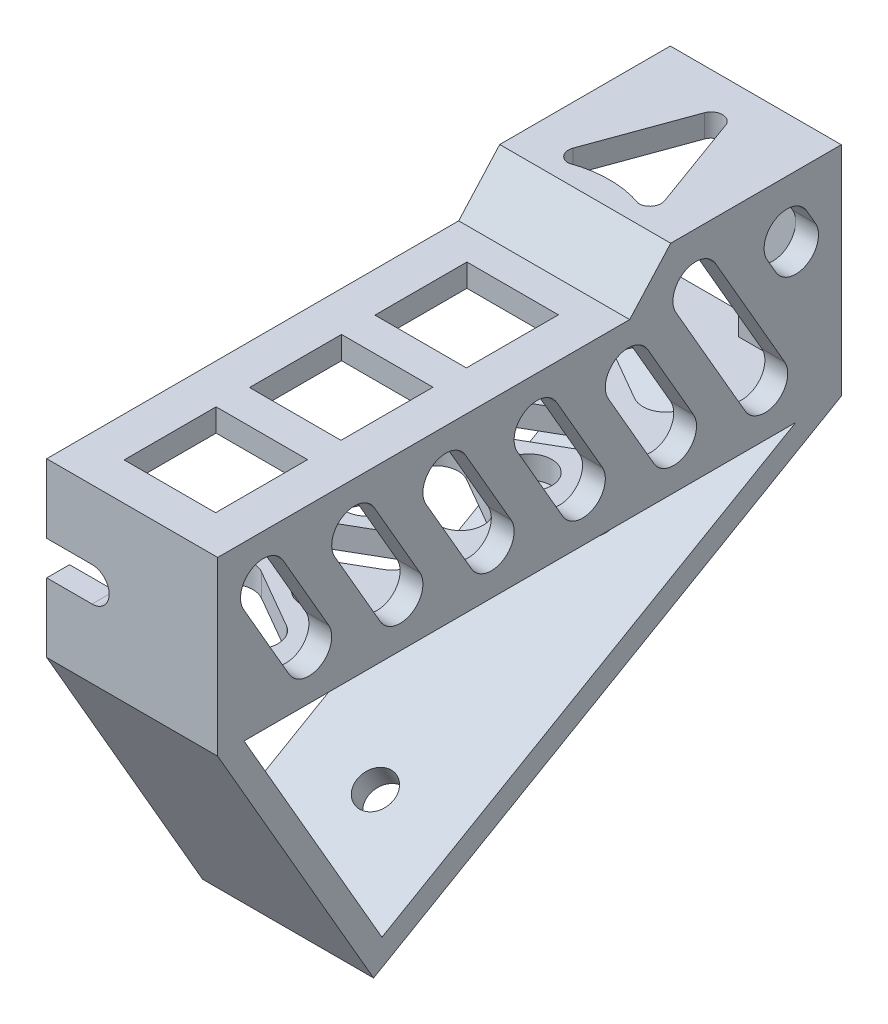
SolidWorks part; units mm, degrees
ref_plane "前视基准面" through (0, 0, 0) normal (0, 0, 1) x (1, 0, 0)
ref_plane "上视基准面" through (0, 0, 0) normal (0, 1, 0) x (1, 0, 0)
ref_plane "右视基准面" through (0, 0, 0) normal (1, 0, 0) x (0, 0, -1)
other "Configuration Table"
sketch "草图1" plane through (0, 0, 0) normal (1, 0, 0) x (0, 0, -1)
  line L0 (13.3, 15) -> (9.7, 11) construction
  line L1 (9.7, 11) -> (-25.3, 11) construction
  line L2 (-25.3, 11) -> (-25.3, 0) construction
  line L3 (-25.3, 0) -> (25.3, 0) construction
  line L4 (25.3, 0) -> (25.3, 15) construction
  line L5 (25.3, 15) -> (13.3, 15) construction
  line L12 (13.2777, 15.05) -> (9.6777, 11.05)
  line L13 (9.6777, 11.05) -> (-25.35, 11.05)
  line L14 (-25.35, 11.05) -> (-25.35, -0.05)
  line L15 (-25.35, -0.05) -> (25.35, -0.05)
  line L16 (25.35, -0.05) -> (25.35, 15.05)
  line L17 (25.35, 15.05) -> (13.2777, 15.05)
  line L18 (12.387, 17.05) -> (8.787, 13.05)
  line L19 (8.787, 13.05) -> (-27.35, 13.05)
  line L20 (-27.35, 13.05) -> (-27.35, -2.05)
  line L21 (-27.35, -2.05) -> (27.35, -2.05)
  line L22 (27.35, -2.05) -> (27.35, 17.05)
  line L23 (27.35, 17.05) -> (12.387, 17.05)
  point P7 (0, 0)
  dimension "D1" = 50.6
  dimension "D2" = 15
  dimension "D3" = 12
  dimension "D4" = 35
  dimension "D5" = 11
  dimension "D6" = 0.05
  dimension "D7" = 2
extrude "凸台-拉伸1" add sketch "草图1" against normal blind 15 contours L16 L17 L12 L13 L14 L15 | L12 L13 L14 L15 L16 L17 | L18 L19 L20 L21 L22 L23 region at (0, 6.1699, -1.6492)
sketch "草图2" plane through (0, 0, 27.35) normal (0, 0, 1) x (1, 0, 0)
  line L0 (0, 5.5) -> (-15, 5.5) construction
  line L1 (-11.02, 7) -> (-15, 7)
  line L2 (-11.02, 4) -> (-15, 4)
  line L3 (-15, 7) -> (-15, 4)
  line L4 (0, -2.05) -> (0, 13.05)
  line L5 (-15, -2.05) -> (0, -2.05)
  line L6 (-15, 13.05) -> (-15, -2.05)
  line L7 (0, 13.05) -> (-15, 13.05)
  line L8 (0, -2.05) -> (0, 13.05) construction
  line L9 (-15, -2.05) -> (0, -2.05) construction
  line L10 (-15, 13.05) -> (-15, -2.05) construction
  line L11 (0, 13.05) -> (-15, 13.05) construction
  circle A0 centre (-11.02, 5.5) radius 1.5
  line M14 (-15, 13.05) -> (-15, -2.05)
  dimension "D2" = 3
  dimension "D3" = 11.02
  dimension "D1" = 0
sketch "草图3" plane through (0, 0, 0) normal (1, 0, 0) x (0, 0, -1)
  line L0 (27.35, -2.05) -> (-27.35, -2.05)
  line L2 (-13.675, -25.7358) -> (27.35, -2.05)
  line L3 (-12.9429, -23.0037) -> (23.35, -2.05)
  line L6 (-27.35, -2.05) -> (-13.675, -25.7358)
  line L7 (-25.0406, -2.05) -> (-12.9429, -23.0037)
  dimension "D1" = 30
  dimension "D2" = 2
  dimension "D3" = 2
extrude "凸台-拉伸3" add sketch "草图3" against normal blind 15 contours L0 L2 L3 region at (0, -13.3767, -6.5395)
sketch "草图4" plane through (0, 0, -27.35) normal (0, 0, -1) x (-1, 0, 0)
  line L0 (-7, 17.05) -> (-7, -2.05) construction
  line L1 (7, 15.05) -> (7, -0.05)
  line L2 (15, 15.05) -> (-7, 15.05)
  line L3 (15, 15.05) -> (15, -0.05)
  line L4 (0, 17.05) -> (0, -2.05)
  line L5 (15, 17.05) -> (0, 17.05)
  line L6 (15, -2.05) -> (15, 17.05)
  line L7 (0, -2.05) -> (15, -2.05)
  line L8 (0, 17.05) -> (0, -2.05) construction
  line L9 (15, 17.05) -> (0, 17.05) construction
  line L10 (15, -2.05) -> (15, 17.05) construction
  line L12 (15, -0.05) -> (-7, -0.05)
  line L13 (-7, 15.05) -> (-7, -0.05)
  line L14 (15, 15.05) -> (-7, -0.05) construction
  line L15 (15, -0.05) -> (-7, 15.05) construction
  line L19 (0, -2.05) -> (15, -2.05)
  point P10 (4, 7.5)
  line M16 (15, -2.05) -> (15, 17.05)
  dimension "D2" = 7
  dimension "D3" = 2
  dimension "D4" = 7
  dimension "D1" = 0
extrude "凸台-拉伸4" add sketch "草图1<4>" against normal blind 2 contours L16 L17 L12 L13 L14 L15 region at (0, 6.1699, -1.6492)
sketch "草图1<4>" plane through (0, 0, 0) normal (1, 0, 0) x (0, 0, -1) same geometry as "草图1"
extrude "切除-拉伸1" cut sketch "草图2" against normal up to next contours A0 | A0 L1 L2 M14 region at (-13.579, 5.5, 27.35) region at (-11.02, 5.5, 27.35)
extrude "切除-拉伸4" cut sketch "草图4" against normal up to next contours L12 L2 L1 M16 region at (-11, 7.5, -27.35)
ref_plane "基准面1" through (-15, -2.05, -27.35) normal (0, 0.5, -0.866) x (-1, 0, 0)
sketch "草图6" plane through (0, -13.3804, -7.7252) normal (0, -0.866, -0.5) x (1, 0, 0)
  line L0 (-7.5, 24.7108) -> (-7.5, -22.6608) construction
  line L4 (0, -22.6608) -> (0, 24.7108)
  line L5 (0, 24.7108) -> (-15, 24.7108)
  line L6 (-15, 24.7108) -> (-15, -22.6608)
  line L7 (-15, -22.6608) -> (0, -22.6608)
  line L8 (0, -22.6608) -> (0, 24.7108) construction
  line L9 (0, 24.7108) -> (-15, 24.7108) construction
  line L10 (-15, 24.7108) -> (-15, -22.6608) construction
  line L11 (-15, -22.6608) -> (0, -22.6608) construction
  circle A0 centre (-7.5, 14.7108) radius 1.6
  circle A1 centre (-7.5, -7.6608) radius 1.6
  dimension "D3" = 3.2
  dimension "D5" = 3.2
  dimension "D2" = 10
  dimension "D4" = 15
  dimension "D1" = 0
extrude "切除-拉伸5" cut sketch "草图6" against normal up to next
sketch "草图9" plane through (0, 0, 0) normal (1, 0, 0) x (0, 0, -1)
  line L0 (-27.35, 5.5) -> (27.35, 5.5) construction
  line L1 (-27.35, 13.05) -> (-27.35, -2.05) construction
  line L2 (27.35, -2.05) -> (27.35, 17.05) construction
  line L3 (-23.35, 8.9641) -> (-19.35, 2.0359) construction
  line L4 (-21.6179, 9.9641) -> (-17.6179, 3.0359)
  line L5 (-25.0821, 7.9641) -> (-21.0821, 1.0359)
  line L6 (-15.35, 8.9641) -> (-11.35, 2.0359) construction
  line L7 (-13.6179, 9.9641) -> (-9.6179, 3.0359)
  line L8 (-17.0821, 7.9641) -> (-13.0821, 1.0359)
  line L9 (-7.35, 8.9641) -> (-3.35, 2.0359) construction
  line L10 (-5.6179, 9.9641) -> (-1.6179, 3.0359)
  line L11 (-9.0821, 7.9641) -> (-5.0821, 1.0359)
  line L12 (0.65, 8.9641) -> (4.65, 2.0359) construction
  line L13 (2.3821, 9.9641) -> (6.3821, 3.0359)
  line L14 (-1.0821, 7.9641) -> (2.9179, 1.0359)
  line L15 (8.65, 8.9641) -> (12.65, 2.0359) construction
  line L16 (10.3821, 9.9641) -> (14.3821, 3.0359)
  line L17 (6.9179, 7.9641) -> (10.9179, 1.0359)
  line L18 (14.5797, 12.55) -> (20.65, 2.0359) construction
  line L19 (16.3117, 13.55) -> (22.3821, 3.0359)
  line L20 (12.8476, 11.55) -> (18.9179, 1.0359)
  line L21 (27.35, 17.05) -> (12.387, 17.05) construction
  line L22 (22.5797, 12.55) -> (23.35, 11.2158) construction
  line L23 (24.3117, 13.55) -> (25.0821, 12.2158)
  line L24 (20.8476, 11.55) -> (21.6179, 10.2158)
  arc A0 (-21.6179, 9.9641) -> (-25.0821, 7.9641) centre (-23.35, 8.9641) ccw
  arc A1 (-21.0821, 1.0359) -> (-17.6179, 3.0359) centre (-19.35, 2.0359) ccw
  arc A2 (-13.6179, 9.9641) -> (-17.0821, 7.9641) centre (-15.35, 8.9641) ccw
  arc A3 (-13.0821, 1.0359) -> (-9.6179, 3.0359) centre (-11.35, 2.0359) ccw
  arc A4 (-5.6179, 9.9641) -> (-9.0821, 7.9641) centre (-7.35, 8.9641) ccw
  arc A5 (-5.0821, 1.0359) -> (-1.6179, 3.0359) centre (-3.35, 2.0359) ccw
  arc A6 (2.3821, 9.9641) -> (-1.0821, 7.9641) centre (0.65, 8.9641) ccw
  arc A7 (2.9179, 1.0359) -> (6.3821, 3.0359) centre (4.65, 2.0359) ccw
  arc A8 (10.3821, 9.9641) -> (6.9179, 7.9641) centre (8.65, 8.9641) ccw
  arc A9 (10.9179, 1.0359) -> (14.3821, 3.0359) centre (12.65, 2.0359) ccw
  arc A10 (16.3117, 13.55) -> (12.8476, 11.55) centre (14.5797, 12.55) ccw
  arc A11 (18.9179, 1.0359) -> (22.3821, 3.0359) centre (20.65, 2.0359) ccw
  arc A12 (24.3117, 13.55) -> (20.8476, 11.55) centre (22.5797, 12.55) ccw
  arc A13 (21.6179, 10.2158) -> (25.0821, 12.2158) centre (23.35, 11.2158) ccw
  point P8 (-21.35, 5.5)
  point P13 (22.9648, 11.8829)
  point P17 (-13.35, 5.5)
  point P24 (-5.35, 5.5)
  point P31 (2.65, 5.5)
  point P38 (10.65, 5.5)
  point P46 (17.6148, 7.2929)
  point P53 (0, 0)
  point P54 (23.724, 11.001)
  dimension "D1" = 2
  dimension "D7" = 2
  dimension "D10" = 2
  dimension "D2" = 8
  dimension "D3" = 5
  dimension "D4" = 4
  dimension "D5" = 60
  dimension "D6" = 8
  dimension "D8" = 8
  dimension "D9" = 4.5
  dimension "D11" = 8
  dimension "D12" = 4
extrude "侧边" cut sketch "草图9" against normal up to next
sketch "草图10" plane through (0, 17.05, 0) normal (0, 1, 0) x (1, 0, 0)
  line L0 (-7.5, 27.35) -> (-7.5, -27.35) construction
  line L1 (-15, 27.35) -> (0, 27.35) construction
  line L2 (-15, -27.35) -> (0, -27.35) construction
  line L3 (-11.9998, 13.987) -> (-3.0002, 13.987) construction
  line L4 (-3.0002, 13.987) -> (-7.5, 26.35) construction
  line L5 (-7.5, 26.35) -> (-11.9998, 13.987) construction
  line L6 (-15, 12.387) -> (0, 12.387) construction
  line L7 (-11.5113, 15.329) -> (-8.4397, 23.7682)
  line L8 (-6.5603, 23.7682) -> (-3.4887, 15.329)
  line L9 (-4.4284, 13.987) -> (-10.5716, 13.987) construction
  line L10 (-3.4887, -13.0472) -> (-3.4887, -4.9788)
  line L11 (-11.5113, -2.0472) -> (-3.4887, -2.0472)
  line L12 (-11.5113, -2.0472) -> (-11.5113, 6.0212)
  line L13 (-11.5113, 6.0212) -> (-3.4887, 6.0212)
  line L14 (-3.4887, -2.0472) -> (-3.4887, 6.0212)
  line L15 (-11.5113, -2.0472) -> (-3.4887, 6.0212) construction
  line L16 (-11.5113, 6.0212) -> (-3.4887, -2.0472) construction
  line L17 (-11.5113, -13.0472) -> (-11.5113, -4.9788)
  line L18 (-11.5113, -13.0472) -> (-3.4887, -13.0472)
  line L19 (-11.5113, -4.9788) -> (-3.4887, -4.9788)
  line L20 (-3.4887, -24.0472) -> (-3.4887, -15.9788)
  line L21 (-11.5113, -24.0472) -> (-11.5113, -15.9788)
  line L22 (-11.5113, -24.0472) -> (-3.4887, -24.0472)
  line L23 (-11.5113, -15.9788) -> (-3.4887, -15.9788)
  line L24 (-15, 8.787) -> (0, 8.787) construction
  arc A0 (-3.4887, 15.329) -> (-4.4284, 13.987) centre (-4.4284, 14.987) cw
  arc A1 (-11.5113, 15.329) -> (-10.5716, 13.987) centre (-10.5716, 14.987) ccw
  arc A2 (-8.4397, 23.7682) -> (-6.5603, 23.7682) centre (-7.5, 23.4262) cw
  arc A3 (-10.5716, 13.987) -> (-4.4284, 13.987) centre (-7.5, 5.5274) cw
  point P9 (-7.5, 13.987)
  point P22 (-7.5, 1.987)
  point P37 (-11.5113, 1.987)
  point P38 (-11.5113, -9.013)
  point P39 (-6.6359, -7.5505)
  point P40 (-3.4887, -8.6385)
  dimension "D4" = 1
  dimension "D5" = 9
  dimension "D1" = 70
  dimension "D2" = 1.6
  dimension "D3" = 1
  dimension "D6" = 8.0684
  dimension "D7" = 8.0226
  dimension "D9" = 6.8
  dimension "D10" = 11
  dimension "D8" = 3
extrude "顶部" cut sketch "草图10" against normal up to next
sketch "草图11" plane through (0, -0.05, 0) normal (0, 1, 0) x (1, 0, 0)
  line L0 (-11.0981, 20.85) -> (-5.9019, 17.85) construction
  line L1 (-10.0981, 22.5821) -> (-4.9019, 19.5821)
  line L2 (-12.0981, 19.1179) -> (-6.9019, 16.1179)
  line L3 (-11.0981, 8.85) -> (-5.9019, 11.85) construction
  line L4 (-12.0981, 10.5821) -> (-6.9019, 13.5821)
  line L5 (-10.0981, 7.1179) -> (-4.9019, 10.1179)
  line L6 (-2, -25.35) -> (-2, 25.35)
  line L7 (-2, 25.35) -> (-7, 25.35)
  line L8 (-7, 25.35) -> (-7, 27.35)
  line L9 (-7, 27.35) -> (-15, 27.35)
  line L10 (-15, 27.35) -> (-15, -25.35)
  line L11 (-15, -25.35) -> (-2, -25.35)
  line L12 (-2, -25.35) -> (-2, 25.35) construction
  line L13 (-2, 25.35) -> (-7, 25.35) construction
  line L14 (-7, 25.35) -> (-7, 27.35) construction
  line L15 (-7, 27.35) -> (-15, 27.35) construction
  line L16 (-15, 27.35) -> (-15, -25.35) construction
  line L17 (-15, -25.35) -> (-2, -25.35) construction
  line L18 (-8.5, -25.35) -> (-8.5, 27.35) construction
  line L19 (-11.0981, 2.85) -> (-5.9019, -0.15) construction
  line L20 (-10.0981, 4.5821) -> (-4.9019, 1.5821)
  line L21 (-12.0981, 1.1179) -> (-6.9019, -1.8821)
  line L22 (-11.0981, -9.15) -> (-5.9019, -6.15) construction
  line L23 (-12.0981, -7.4179) -> (-6.9019, -4.4179)
  line L24 (-10.0981, -10.8821) -> (-4.9019, -7.8821)
  line L25 (-11.0981, -15.15) -> (-5.9019, -18.15) construction
  line L26 (-10.0981, -13.4179) -> (-4.9019, -16.4179)
  line L27 (-12.0981, -16.8821) -> (-6.9019, -19.8821)
  line L28 (-15, 14.85) -> (-2, 14.85) construction
  line L34 (-15, 5.85) -> (-2, 5.85) construction
  line L35 (-11.0981, -27.15) -> (-5.9019, -24.15) construction
  line L36 (-12.0981, -25.4179) -> (-6.9019, -22.4179) [skipped]
  line L37 (-10.0981, -28.8821) -> (-4.9019, -25.8821) [skipped]
  line L38 (-11.0981, -27.15) -> (-5.9019, -24.15) construction
  line L39 (-12.0981, -25.4179) -> (-6.9019, -22.4179) [skipped]
  line L40 (-10.0981, -28.8821) -> (-4.9019, -25.8821) [skipped]
  arc A0 (-10.0981, 22.5821) -> (-12.0981, 19.1179) centre (-11.0981, 20.85) ccw
  arc A1 (-6.9019, 16.1179) -> (-4.9019, 19.5821) centre (-5.9019, 17.85) ccw
  arc A2 (-12.0981, 10.5821) -> (-10.0981, 7.1179) centre (-11.0981, 8.85) ccw
  arc A3 (-4.9019, 10.1179) -> (-6.9019, 13.5821) centre (-5.9019, 11.85) ccw
  arc A4 (-10.0981, 4.5821) -> (-12.0981, 1.1179) centre (-11.0981, 2.85) ccw
  arc A5 (-6.9019, -1.8821) -> (-4.9019, 1.5821) centre (-5.9019, -0.15) ccw
  arc A6 (-12.0981, -7.4179) -> (-10.0981, -10.8821) centre (-11.0981, -9.15) ccw
  arc A7 (-4.9019, -7.8821) -> (-6.9019, -4.4179) centre (-5.9019, -6.15) ccw
  arc A8 (-10.0981, -13.4179) -> (-12.0981, -16.8821) centre (-11.0981, -15.15) ccw
  arc A9 (-6.9019, -19.8821) -> (-4.9019, -16.4179) centre (-5.9019, -18.15) ccw
  circle A14 centre (-11.0981, 14.85) radius 2
  circle A15 centre (-5.9019, 5.85) radius 2
  circle A16 centre (-11.0981, -3.15) radius 2
  circle A17 centre (-5.9019, -12.15) radius 2
  circle A18 centre (-11.0981, -21.15) radius 2
  circle A20 centre (-5.9019, -30.15) radius 2 [skipped]
  arc A23 (-12.0981, -25.4179) -> (-10.0981, -28.8821) centre (-11.0981, -27.15) ccw [skipped]
  arc A24 (-4.9019, -25.8821) -> (-6.9019, -22.4179) centre (-5.9019, -24.15) ccw [skipped]
  point P6 (-8.5, 19.35)
  point P15 (-8.5, 10.35)
  point P26 (-8.5, 1.35)
  point P33 (-8.5, -7.65)
  point P40 (-8.5, -16.65)
  point P51 (0, 0)
  point P52 (-8.5, -25.65)
  point P72 (-8.5, -25.65)
  point P79 (-8.5, -25.65)
  dimension "D2" = 2
  dimension "D3" = 2
  dimension "D12" = 4
  dimension "D14" = 4
  dimension "D4" = 6
  dimension "D5" = 6
  dimension "D6" = 60
  dimension "D7" = 60
  dimension "D8" = 9
  dimension "D9" = 8
  dimension "D11" = 9
  dimension "D13" = 4.5
  dimension "D16" = 6
  dimension "D1" = 0
  dimension "D10" = 3
  dimension "D15" = 3
extrude "底部" cut sketch "草图11" against normal up to next
